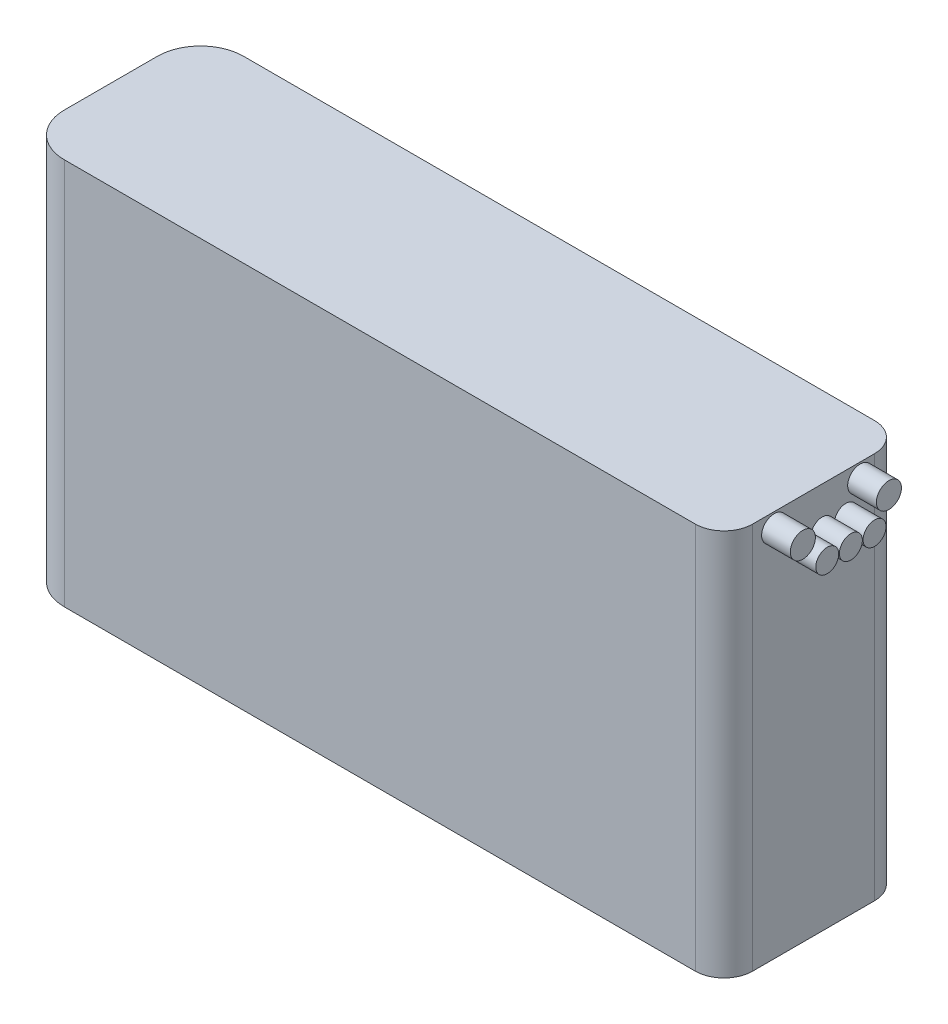
SolidWorks part; units mm, degrees
ref_plane "Ebene vorne" through (0, 0, 0) normal (0, 0, 1) x (1, 0, 0)
ref_plane "Ebene oben" through (0, 0, 0) normal (0, 1, 0) x (1, 0, 0)
ref_plane "Ebene rechts" through (0, 0, 0) normal (1, 0, 0) x (0, 0, -1)
sketch "Skizze1" plane through (0, 0, 0) normal (0, 0, 1) x (1, 0, 0)
  line L1 (0, 0) -> (49, 0)
  line L2 (0, 0) -> (0, 27)
  line L3 (0, 27) -> (49, 27)
  line L4 (49, 0) -> (49, 27)
  dimension "D1" = 49
  dimension "D2" = 27
extrude "Aufsatz-Linear austragen1" add sketch "Skizze1" along normal blind 12.5
fillet "Verrundung1" radius 2 2 edges at (49, 13.5, 0) (49, 13.5, 12.5)
fillet "Verrundung2" radius 3 2 edges at (0, 13.5, 12.5) (0, 13.5, 0)
sketch "Skizze3" plane through (49, 0, 0) normal (1, 0, 0) x (0, 0, -1)
  line L0 (-10.5, 27) -> (-2, 27) construction
  line L1 (0, 27) -> (0, 0) construction
  line L2 (-7.3, 24.2) -> (-5.65, 24.2) construction
  line L3 (-5.65, 24.2) -> (-4, 24.2) construction
  circle A0 centre (-9, 26) radius 0.875
  circle A1 centre (-3, 26) radius 0.875
  circle A2 centre (-4, 24.2) radius 0.8
  circle A3 centre (-5.65, 24.2) radius 0.8
  circle A4 centre (-7.3, 24.2) radius 0.8
  dimension "D1" = 1.75
  dimension "D6" = 1.6
  dimension "D2" = 1
  dimension "D3" = 6
  dimension "D4" = 3
  dimension "D5" = 1.65
  dimension "D7" = 4
  dimension "D8" = 1.8
extrude "Aufsatz-Linear austragen2" add sketch "Skizze3" along normal blind 2
